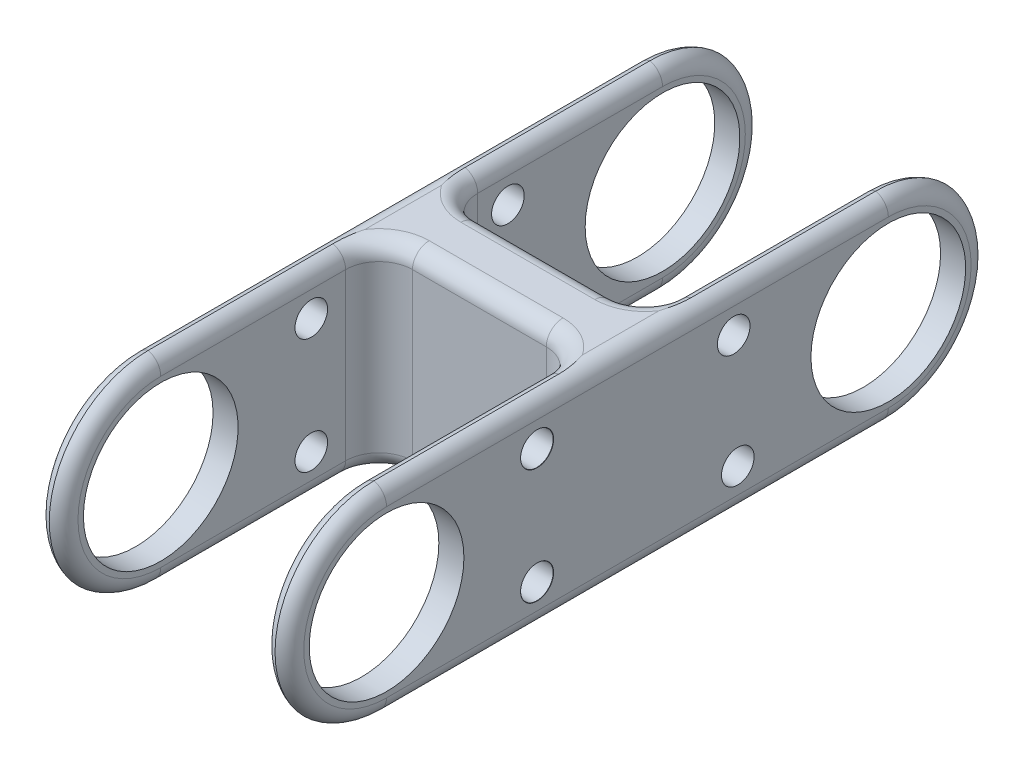
SolidWorks part; units mm, degrees
ref_plane "Front Plane" through (0, 0, 0) normal (0, 0, 1) x (1, 0, 0)
ref_plane "Top Plane" through (0, 0, 0) normal (0, 1, 0) x (1, 0, 0)
ref_plane "Right Plane" through (0, 0, 0) normal (1, 0, 0) x (0, 0, -1)
sketch "Sketch1" plane through (0, 0, 0) normal (1, 0, 0) x (0, 0, -1)
  line L0 (0, 11.9) -> (60, 11.9)
  line L1 (0, -11.9) -> (60, -11.9)
  line L2 (30, 11.9) -> (30, -11.9) construction
  circle A0 centre (0, 0) radius 9.25
  arc A1 (0, 11.9) -> (0, -11.9) centre (0, 0) ccw
  circle A2 centre (60, 0) radius 9.25
  arc A3 (60, 11.9) -> (60, -11.9) centre (60, 0) cw
  dimension "D1" = 18.5
  dimension "D2" = 23.8
  dimension "D3" = 60
extrude "Boss-Extrude1" add sketch "Sketch1" along normal blind 30
sketch "Sketch2" plane through (0, 11.9, 0) normal (0, 1, 0) x (1, 0, 0)
  line L0 (0, -11.9) -> (30, -11.9) construction
  line L1 (3, -11.9) -> (27, -11.9)
  line L2 (3, -11.9) -> (3, 26.1)
  line L3 (3, 26.1) -> (27, 26.1)
  line L4 (27, -11.9) -> (27, 26.1)
  line L5 (0, 30) -> (30, 30) construction
  line L6 (0, 60) -> (0, 0) construction
  line L7 (30, 60) -> (30, 0) construction
  line L8 (3, 33.9) -> (27, 33.9)
  line L9 (27, 71.9) -> (27, 33.9)
  line L10 (3, 71.9) -> (27, 71.9)
  line L11 (3, 71.9) -> (3, 33.9)
  dimension "D1" = 38
  dimension "D2" = 3
  dimension "D3" = 3
extrude "Cut-Extrude1" cut sketch "Sketch2" against normal through all
ref_plane "Plane1" through (0, 0, -30) normal (0, 0, 1) x (1, 0, 0)
fillet "Fillet1" radius 4 4 edges at (27, 0, -26.1) (3, 0, -26.1) (27, 0, -33.9) (3, 0, -33.9)
hole_wizard "M3.5 Clearance Hole1" positions "Sketch3" profile "Sketch4" hole size "M3.5" standard "ANSI Metric" end condition through all
sketch "Sketch3" plane through (0, 0, 0) normal (-1, 0, 0) x (0, 0, 1)
  circle A0 centre (-41.511, 6.9) radius 1.7024 construction
  point P0 (-42, -6.9)
  point P3 (-41.511, 6.9)
sketch "Sketch4" plane through (0, -6.9, -42) normal (0, 1, 0) x (0, 0, 1)
  line L0 (0, 0) -> (0, 30)
  line L1 (0, 30) -> (1.95, 30)
  line L2 (1.95, 30) -> (1.95, 0.025)
  line L3 (1.95, 0.025) -> (1.975, 0)
  line L5 (1.975, 0) -> (0, 0)
  line L6 (-1.95, 0.025) -> (-1.975, 0) construction
  line L11 (0, -6.35) -> (0, 107.95) construction
  dimension "Thru Hole Dia." = 3.9
  dimension "Thru Hole Depth" = 30
  dimension "Near C'Sink Dia." = 3.95
  dimension "Near C'Sink Angle" = 90
sketch "Sketch5" plane through (0, 0, -33.9) normal (0, 0, -1) x (-1, 0, 0)
  line L0 (-23, 11.9) -> (-23, -11.9) construction
  line L1 (-23, 0) -> (-7, 0) construction
  line L2 (-7, -11.9) -> (-7, 11.9) construction
  line B0 (-23, -3.65) -> (-23, -10.15)
  line B1 (-23, -3.65) -> (-20, -3.65)
  line B2 (-20, -3.65) -> (-20, -10.15)
  line B3 (-23, -10.15) -> (-20, -10.15)
  line B4 (-23, 0) -> (-7, 0) construction
  line B5 (-14.9675, -0.1255) -> (-15, -8.8352) construction
  line B6 (-7.01, -10.2096) -> (-10.0099, -10.1872)
  line B7 (-9.9615, -3.6874) -> (-10.0099, -10.1872)
  line B8 (-6.9616, -3.7098) -> (-9.9615, -3.6874)
  line B9 (-6.9616, -3.7098) -> (-7.01, -10.2096)
  line B10 (-6.9616, 3.7098) -> (-7.01, 10.2096)
  line B11 (-6.9616, 3.7098) -> (-9.9615, 3.6874)
  line B12 (-9.9615, 3.6874) -> (-10.0099, 10.1872)
  line B13 (-7.01, 10.2096) -> (-10.0099, 10.1872)
  line B14 (-23, 10.15) -> (-20, 10.15)
  line B15 (-20, 3.65) -> (-20, 10.15)
  line B16 (-23, 3.65) -> (-20, 3.65)
  line B17 (-23, 3.65) -> (-23, 10.15)
sketch_block_instance "Block1-1"
sketch_block "Block1" parameters "D1"=3, "D2"=6.5
sketch "Sketch6" plane through (30, 0, 0) normal (-1, 0, 0) x (0, 0, 1)
  line L0 (-40.025, -6.9) -> (-43.975, -6.9) construction
  circle A0 centre (-42, -6.9) radius 1.975 construction
hole_wizard "M3.5 Clearance Hole2" positions "Sketch9" profile "Sketch8" hole size "M3.5" standard "ANSI Metric" end condition through all
sketch "Sketch9" plane through (30, 0, 0) normal (1, 0, 0) x (0, 0, -1)
  circle A0 centre (18, -6.9) radius 1.975 construction
  circle A1 centre (18, 6.9) radius 1.975 construction
  circle A2 centre (18, -6.9) radius 1.975 construction
  circle A3 centre (18, 6.9) radius 1.975 construction
  point P0 (18, 6.9)
  point P3 (18, -6.9)
sketch "Sketch8" plane through (30, 6.9, -18) normal (0, 1, 0) x (0, 0, -1)
  line L0 (0, 0) -> (0, 30)
  line L1 (0, 30) -> (1.95, 30)
  line L2 (1.95, 30) -> (1.95, 0.025)
  line L3 (1.95, 0.025) -> (1.975, 0)
  line L5 (1.975, 0) -> (0, 0)
  line L6 (-1.95, 0.025) -> (-1.975, 0) construction
  line L11 (0, -6.35) -> (0, 107.95) construction
  dimension "Thru Hole Dia." = 3.9
  dimension "Thru Hole Depth" = 30
  dimension "Near C'Sink Dia." = 3.95
  dimension "Near C'Sink Angle" = 90
sketch "Sketch10" plane through (0, 0, -26.1) normal (0, 0, 1) x (1, 0, 0)
  line L0 (-1.0691, -12.5585) -> (14.9309, -12.5585) construction
  line L1 (23, 0) -> (7, 0) construction
  line L2 (23, -11.9) -> (23, 11.9) construction
  line L3 (7, 11.9) -> (7, -11.9) construction
  line B0 (7, -3.65) -> (7, -10.15)
  line B1 (7, -3.65) -> (10, -3.65)
  line B2 (10, -3.65) -> (10, -10.15)
  line B3 (7, -10.15) -> (10, -10.15)
  line B4 (7, 0) -> (23, 0) construction
  line B5 (15.0325, -0.1255) -> (15, -8.8352) construction
  line B6 (22.99, -10.2096) -> (19.9901, -10.1872)
  line B7 (20.0385, -3.6874) -> (19.9901, -10.1872)
  line B8 (23.0384, -3.7098) -> (20.0385, -3.6874)
  line B9 (23.0384, -3.7098) -> (22.99, -10.2096)
  line B10 (23.0384, 3.7098) -> (22.99, 10.2096)
  line B11 (23.0384, 3.7098) -> (20.0385, 3.6874)
  line B12 (20.0385, 3.6874) -> (19.9901, 10.1872)
  line B13 (22.99, 10.2096) -> (19.9901, 10.1872)
  line B14 (7, 10.15) -> (10, 10.15)
  line B15 (10, 3.65) -> (10, 10.15)
  line B16 (7, 3.65) -> (10, 3.65)
  line B17 (7, 3.65) -> (7, 10.15)
sketch_block_instance "Block1-2"
fillet "Fillet2" [suppressed] radius 2
hole_wizard "M3.5 Clearance Hole3" positions "Sketch11" profile "Sketch12" hole size "M3.5" standard "ANSI Metric" end condition through all
sketch "Sketch11" plane through (30, 0, 0) normal (1, 0, 0) x (0, 0, -1)
  point P0 (18, 6.9)
  point P3 (18, -6.9)
sketch "Sketch12" plane through (30, 6.9, -18) normal (0, 1, 0) x (0, 0, -1)
  line L0 (0, 0) -> (0, 30)
  line L1 (0, 30) -> (1.95, 30)
  line L2 (1.95, 30) -> (1.95, 0.025)
  line L3 (1.95, 0.025) -> (1.975, 0)
  line L5 (1.975, 0) -> (0, 0)
  line L6 (-1.95, 0.025) -> (-1.975, 0) construction
  line L11 (0, -6.35) -> (0, 107.95) construction
  dimension "Thru Hole Dia." = 3.9
  dimension "Thru Hole Depth" = 30
  dimension "Near C'Sink Dia." = 3.95
  dimension "Near C'Sink Angle" = 90
sketch "Sketch13" [suppressed] plane through (0, 0, 0) normal (-1, 0, 0) x (0, 0, 1)
  line L0 (-125.6084, 9.9) -> (-125.6084, -9.9) construction
  line L1 (0, 9.9) -> (-60, 9.9) construction
  line L2 (-60, -9.9) -> (0, -9.9) construction
  point P0 (-128.6084, 6.9)
  dimension "D1" = 3
fillet "Fillet3" radius 2 32 edges at (0, 0, -71.9) (0, -11.9, -30) (0, 0, 11.9) (3, 0, -71.9) (3, -11.9, -48.95) (4.1716, -11.9, -35.0716) (15, -11.9, -33.9) (25.8284, -11.9, -35.0716) (27, -11.9, -48.95) (27, 0, -71.9) (30, 0, -71.9) (30, -11.9, -30) (30, 0, 11.9) (27, 0, 11.9) (27, -11.9, -11.05) (25.8284, -11.9, -24.9284) (15, -11.9, -26.1) (4.1716, -11.9, -24.9284) (3, -11.9, -11.05) (3, 0, 11.9) (0, 11.9, -30) (3, 11.9, -48.95) (4.1716, 11.9, -35.0716) (15, 11.9, -33.9) (25.8284, 11.9, -35.0716) (27, 11.9, -48.95) (30, 11.9, -30) (27, 11.9, -11.05) (25.8284, 11.9, -24.9284) (15, 11.9, -26.1) (4.1716, 11.9, -24.9284) (3, 11.9, -11.05)
